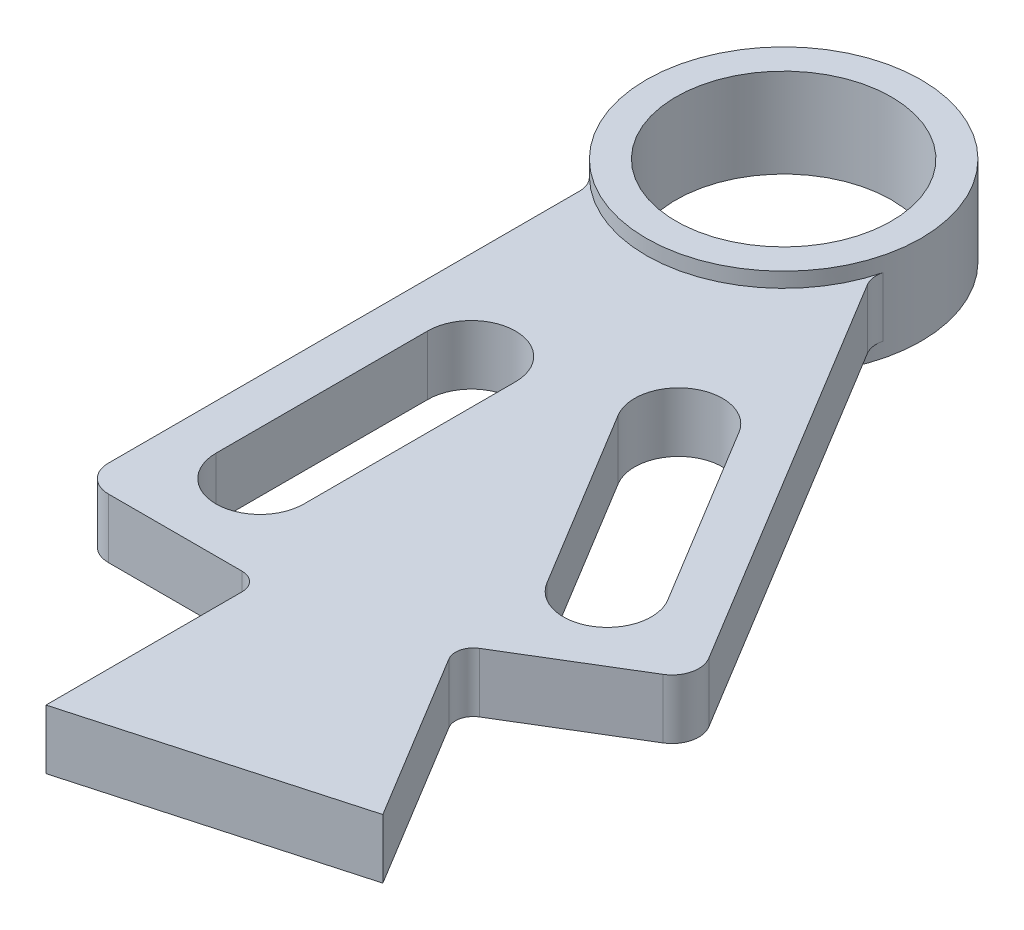
SolidWorks part; units mm, degrees
material "AISI 4130 Steel, annealed at 865C"
ref_plane "Front Plane" through (0, 0, 0) normal (0, 0, 1) x (1, 0, 0)
ref_plane "Top Plane" through (0, 0, 0) normal (0, 1, 0) x (1, 0, 0)
ref_plane "Right Plane" through (0, 0, 0) normal (1, 0, 0) x (0, 0, -1)
sketch "Sketch1" plane through (0, 0, 0) normal (0, 1, 0) x (1, 0, 0)
  line L0 (0, -60.6552) -> (0, -14.6812) construction
  line L1 (31.4453, -51.8676) -> (7.6111, -12.5542) construction
  line L2 (0, -55.9562) -> (0, -33.3502) construction
  line L5 (-4.699, -55.9562) -> (-4.699, -33.3502)
  line L8 (-9.525, -65.4812) -> (9.525, -65.4812)
  line L9 (25.8023, -60.9324) -> (42.0923, -51.0563)
  line L10 (-9.525, -65.4812) -> (-9.525, -11.1719)
  line L11 (42.0923, -51.0563) -> (13.9369, -4.6153)
  line L12 (9.525, -65.4812) -> (9.525, -88.3412)
  line L13 (25.8023, -60.9324) -> (37.6535, -80.4805)
  line L14 (9.525, -88.3412) -> (37.6535, -80.4805)
  line L15 (0, -14.6812) -> (0, 0) construction
  line L16 (0, -65.4812) -> (0, -60.6552) construction
  line L17 (33.9473, -55.9944) -> (31.4453, -51.8676)
  line L18 (4.699, -55.9562) -> (4.699, -33.3502)
  line L19 (17.2897, -28.5185) -> (29.0093, -47.8493) construction
  line L20 (21.3079, -26.0824) -> (33.0275, -45.4132)
  line L21 (13.2715, -30.9546) -> (24.991, -50.2854)
  line L22 (7.6111, -12.5542) -> (0, 0) construction
  line L23 (0, 0) -> (20.5089, -73.3882) construction
  line L25 (184.8058, -304.8281) -> (17.67, -29.1458) construction
  line L27 (0, 0) -> (23.5893, -84.4108) construction
  circle A0 centre (0, 0) radius 11.5062
  circle A1 centre (0, 0) radius 14.6812
  arc A2 (-4.699, -55.9562) -> (4.699, -55.9562) centre (0, -55.9562) ccw
  arc A3 (4.699, -33.3502) -> (-4.699, -33.3502) centre (0, -33.3502) ccw
  arc A4 (21.3079, -26.0824) -> (13.2715, -30.9546) centre (17.2897, -28.5185) ccw
  arc A5 (24.991, -50.2854) -> (33.0275, -45.4132) centre (29.0093, -47.8493) ccw
  point P9 (0, -44.6532)
  point P14 (23.1495, -38.1839)
  point P23 (0, -65.4812)
  point P26 (33.9473, -55.9944)
  point P33 (0, -60.6552)
  point P36 (31.4453, -51.8676)
  point P38 (0, -28.6512)
  dimension "D2" = 29.3624
  dimension "D3" = 50.8
  dimension "D4" = 4.826
  dimension "D6" = 22.86
  dimension "D5" = 4.826
  dimension "D8" = 13.97
  dimension "D9" = 76.2
  dimension "D7" = 9.525
extrude "Bearing extrude" add sketch "Sketch1" along normal mid plane 9.525 contours A1 A0 region at (-5.9782, 0, -12.9529)
extrude "Boss-Extrude2" add sketch "Sketch1<5>" along normal mid plane 6.35 contours A1 L10 L8 L12 L14 L13 L9 L11 A4 A2 region at (13.3713, 0, 47.8474)
sketch "Sketch1<5>" plane through (0, 0, 0) normal (0, 1, 0) x (1, 0, 0) same geometry as "Sketch1"
sketch3d "Tab Point"
  line L0 (20.5089, 0, 73.3882) -> (20.5089, 22.225, 73.3882) construction
  line L1 (0, 0, 0) -> (20.5089, 0, 73.3882) construction
  line L2 (0, 0, 0) -> (23.5893, 0, 84.4108) construction
  dimension "D1" = 22.225
fillet "Fillet1" radius 2.54 2 edges at (13.9369, 0, 4.6153) (-9.525, 0, 11.1719)
fillet "Fillet2" radius 1.905 2 edges at (25.8023, 0, 60.9324) (9.525, 0, 65.4812)
fillet "Fillet3" radius 2.8575 2 edges at (42.0923, 0, 51.0563) (-9.525, 0, 65.4812)
equation "\"Apex_thickness\"= .25"
equation "\"Bearing_diameter\"= .906"
equation "\"A-arm_angle\"= 32.91"
equation "\"D1@Sketch1\"=\"Bearing_diameter\""
equation "\"D1@Boss-Extrude2\"= \"Apex_thickness\""
equation "\"apex slot\"= 1.4"
equation "\"tube diameter\"= 5 / 8"
